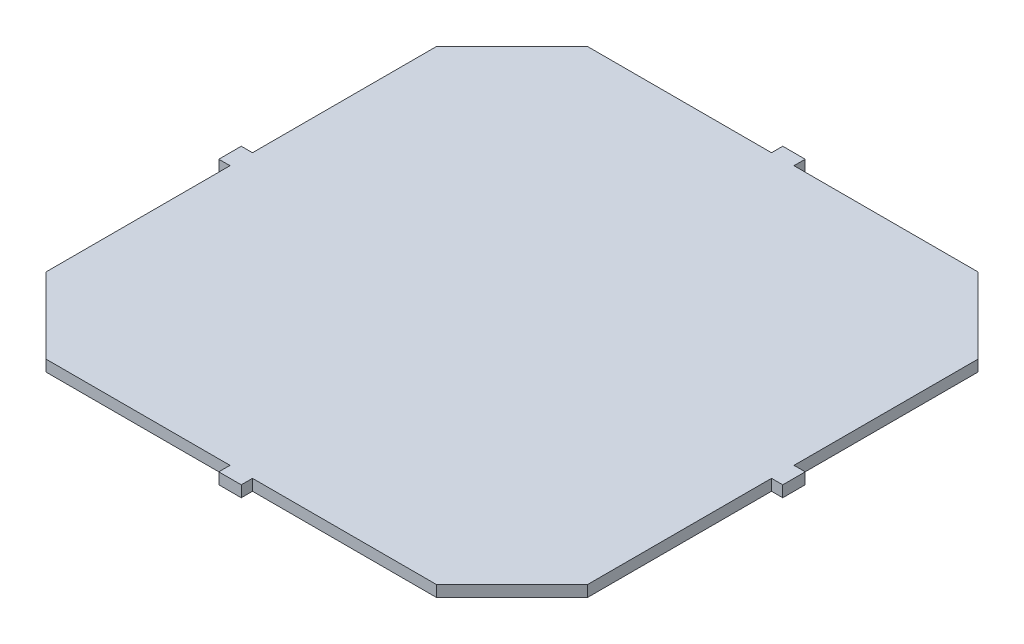
SolidWorks part; units mm, degrees
material "ABS PC"
ref_plane "Front Plane" through (0, 0, 0) normal (0, 0, 1) x (1, 0, 0)
ref_plane "Top Plane" through (0, 0, 0) normal (0, 1, 0) x (1, 0, 0)
ref_plane "Right Plane" through (0, 0, 0) normal (1, 0, 0) x (0, 0, -1)
sketch "Sketch1" plane through (0, 0, 0) normal (0, 1, 0) x (1, 0, 0)
  line L0 (-24.0925, 17.375) -> (-17.375, 24.0925)
  line L1 (-17.375, -24.0925) -> (17.375, -24.0925)
  line L2 (-24.0925, -17.375) -> (-24.0925, 17.375)
  line L3 (-17.375, 24.0925) -> (17.375, 24.0925)
  line L4 (24.0925, -17.375) -> (24.0925, 17.375)
  line L5 (-20.7338, -20.7338) -> (20.7338, 20.7338) construction
  line L6 (-20.7338, 20.7338) -> (20.7338, -20.7338) construction
  line L7 (-24.0925, -17.375) -> (-17.375, -24.0925)
  line L8 (17.375, -24.0925) -> (24.0925, -17.375)
  line L9 (17.375, 24.0925) -> (24.0925, 17.375)
  point P0 (0, 0)
  dimension "D1" = 34.75
  dimension "D2" = 34.75
  dimension "D3" = 135
  dimension "D4" = 135
  dimension "D5" = 9.5
  dimension "D6" = 135
extrude "Boss-Extrude1" add sketch "Sketch1" along normal blind 1
sketch "Sketch2" plane through (0, 1, 0) normal (0, 1, 0) x (1, 0, 0)
  line L0 (0, 24.0925) -> (0, -24.0925) construction
  line L1 (17.375, 24.0925) -> (-17.375, 24.0925) construction
  line L2 (-17.375, -24.0925) -> (17.375, -24.0925) construction
  line L3 (-24.0925, 0) -> (24.0925, 0) construction
  line L4 (-24.0925, 17.375) -> (-24.0925, -17.375) construction
  line L5 (24.0925, -17.375) -> (24.0925, 17.375) construction
  line L6 (-24.0925, 1) -> (-25.0925, 1)
  line L7 (-25.0925, 1) -> (-25.0925, -1)
  line L8 (-25.0925, -1) -> (-24.0925, -1)
  line L9 (-1, 24.0925) -> (-1, 25.0925)
  line L10 (-1, 25.0925) -> (1, 25.0925)
  line L11 (1, 25.0925) -> (1, 24.0925)
  line L12 (1, -25.0925) -> (1, -24.0925)
  line L13 (-1, -25.0925) -> (1, -25.0925)
  line L14 (-1, -24.0925) -> (-1, -25.0925)
  line L15 (25.0925, -1) -> (24.0925, -1)
  line L16 (25.0925, 1) -> (25.0925, -1)
  line L17 (24.0925, 1) -> (25.0925, 1)
  line L18 (-1, 24.0925) -> (1, 24.0925)
  line L19 (24.0925, 1) -> (24.0925, -1)
  line L20 (-1, -24.0925) -> (1, -24.0925)
  line L21 (-24.0925, -1) -> (-24.0925, 1)
  dimension "D1" = 2
  dimension "D2" = 1
  dimension "D3" = 2
  dimension "D4" = 1
extrude "Boss-Extrude2" add sketch "Sketch2" against normal blind 1
